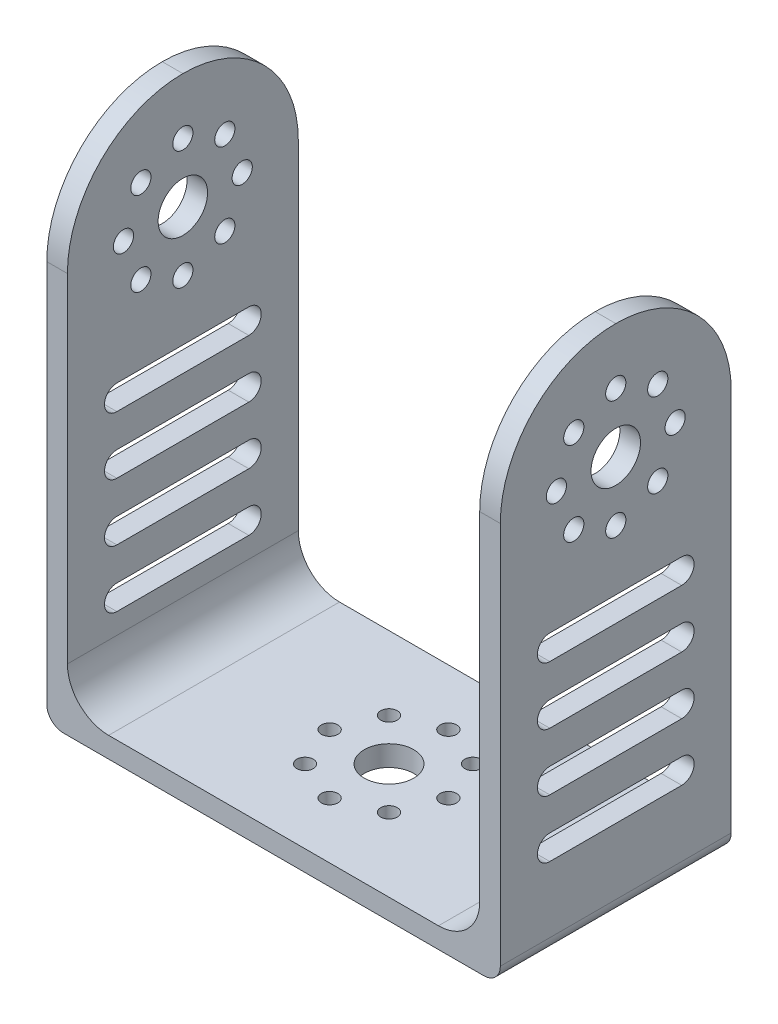
SolidWorks part; units mm, degrees
ref_plane "Plan de face" through (0, 0, 0) normal (0, 0, 1) x (1, 0, 0)
ref_plane "Plan de dessus" through (0, 0, 0) normal (0, 1, 0) x (1, 0, 0)
ref_plane "Plan de droite" through (0, 0, 0) normal (1, 0, 0) x (0, 0, -1)
sketch "Esquisse1" plane through (0, 0, 0) normal (0, 1, 0) x (1, 0, 0)
  line L1 (0, 0) -> (55, 0)
  line L2 (0, 0) -> (0, 28)
  line L3 (0, 28) -> (55, 28)
  line L4 (55, 0) -> (55, 28)
  circle A0 centre (22.4088, 19.0912) radius 1
  circle A1 centre (27.5, 21.2) radius 1
  circle A2 centre (32.5912, 19.0912) radius 1
  circle A3 centre (34.7, 14) radius 1
  circle A4 centre (32.5912, 8.9088) radius 1
  circle A5 centre (27.5, 6.8) radius 1
  circle A6 centre (22.4088, 8.9088) radius 1
  circle A7 centre (20.3, 14) radius 1
  circle A8 centre (27.5, 14) radius 3
  point P8 (27.5, 14)
  point P16 (27.5, 14)
  dimension "D7" = 2
  dimension "D8" = 6
  dimension "D1" = 55
  dimension "D2" = 28
  dimension "D3" = 27.5
  dimension "D4" = 14
  dimension "D5" = 7.2
  dimension "D6" = 8
extrude "Boss.-Extru.1" add sketch "Esquisse1" along normal blind 2.5
sketch "Esquisse2" plane through (0, 2.5, 0) normal (0, 1, 0) x (1, 0, 0)
  line L0 (0, 0) -> (55, 0) construction
  line L1 (0, 28) -> (2.5, 28)
  line L2 (0, 28) -> (0, 0)
  line L3 (0, 0) -> (2.5, 0)
  line L4 (2.5, 28) -> (2.5, 0)
  line L6 (55, 28) -> (52.5, 28)
  line L7 (55, 28) -> (55, 0)
  line L8 (55, 0) -> (52.5, 0)
  line L9 (52.5, 28) -> (52.5, 0)
  dimension "D1" = 2.5
  dimension "D2" = 2.5
extrude "Boss.-Extru.2" add sketch "Esquisse2" along normal blind 60
fillet "Congé1" radius 5 2 edges at (52.5, 2.5, -14)
fillet "Congé2" radius 2 2 edges at (0, 0, -14) (55, 0, -14)
sketch "Esquisse3" plane through (55, 0, 0) normal (1, 0, 0) x (0, 0, -1)
  line L0 (22, 11.5) -> (6, 11.5) construction
  line L1 (22, 10) -> (6, 10)
  line L2 (22, 13) -> (6, 13)
  line L3 (22, 18.5) -> (6, 18.5) construction
  line L4 (22, 17) -> (6, 17)
  line L5 (22, 20) -> (6, 20)
  line L6 (22, 25.5) -> (6, 25.5) construction
  line L7 (22, 24) -> (6, 24)
  line L8 (22, 27) -> (6, 27)
  line L9 (22, 32.5) -> (6, 32.5) construction
  line L10 (22, 31) -> (6, 31)
  line L11 (22, 34) -> (6, 34)
  line L12 (0, 62.5) -> (28, 62.5) construction
  line L13 (0, 62.5) -> (0, 2) construction
  arc A0 (22, 10) -> (22, 13) centre (22, 11.5) ccw
  arc A1 (6, 13) -> (6, 10) centre (6, 11.5) ccw
  arc A2 (22, 17) -> (22, 20) centre (22, 18.5) ccw
  arc A3 (6, 20) -> (6, 17) centre (6, 18.5) ccw
  arc A4 (22, 24) -> (22, 27) centre (22, 25.5) ccw
  arc A5 (6, 27) -> (6, 24) centre (6, 25.5) ccw
  arc A6 (22, 31) -> (22, 34) centre (22, 32.5) ccw
  arc A7 (6, 34) -> (6, 31) centre (6, 32.5) ccw
  circle A8 centre (14, 41.3) radius 1.2249
  circle A9 centre (8.9088, 43.4088) radius 1.2249
  circle A10 centre (6.8, 48.5) radius 1.2249
  circle A11 centre (8.9088, 53.5912) radius 1.2249
  circle A12 centre (14, 55.7) radius 1.2249
  circle A13 centre (19.0912, 53.5912) radius 1.2249
  circle A14 centre (21.2, 48.5) radius 1.2249
  circle A15 centre (19.0912, 43.4088) radius 1.2249
  circle A16 centre (14, 48.5) radius 3
  point P2 (14, 11.5)
  point P9 (14, 18.5)
  point P16 (14, 25.5)
  point P23 (14, 32.5)
  point P32 (14, 48.5)
  point P52 (14, 48.5)
  dimension "D10" = 1.5
  dimension "D11" = 1.5
  dimension "D12" = 1.5
  dimension "D14" = 7.2
  dimension "D15" = 14
  dimension "D22" = 6
  dimension "D1" = 30
  dimension "D2" = 7
  dimension "D3" = 7
  dimension "D4" = 7
  dimension "D5" = 14
  dimension "D6" = 14
  dimension "D7" = 14
  dimension "D8" = 14
  dimension "D9" = 3
  dimension "D13" = 14
  dimension "D16" = 14
  dimension "D18" = 16
  dimension "D19" = 16
  dimension "D20" = 16
  dimension "D21" = 16
  dimension "D17" = 8
extrude "Enlèv. mat.-Extru.1" cut sketch "Esquisse3" against normal blind 55
fillet "Congé3" radius 14 4 edges at (1.25, 62.5, 0) (53.75, 62.5, -28) (53.75, 62.5, 0) (1.25, 62.5, -28)
